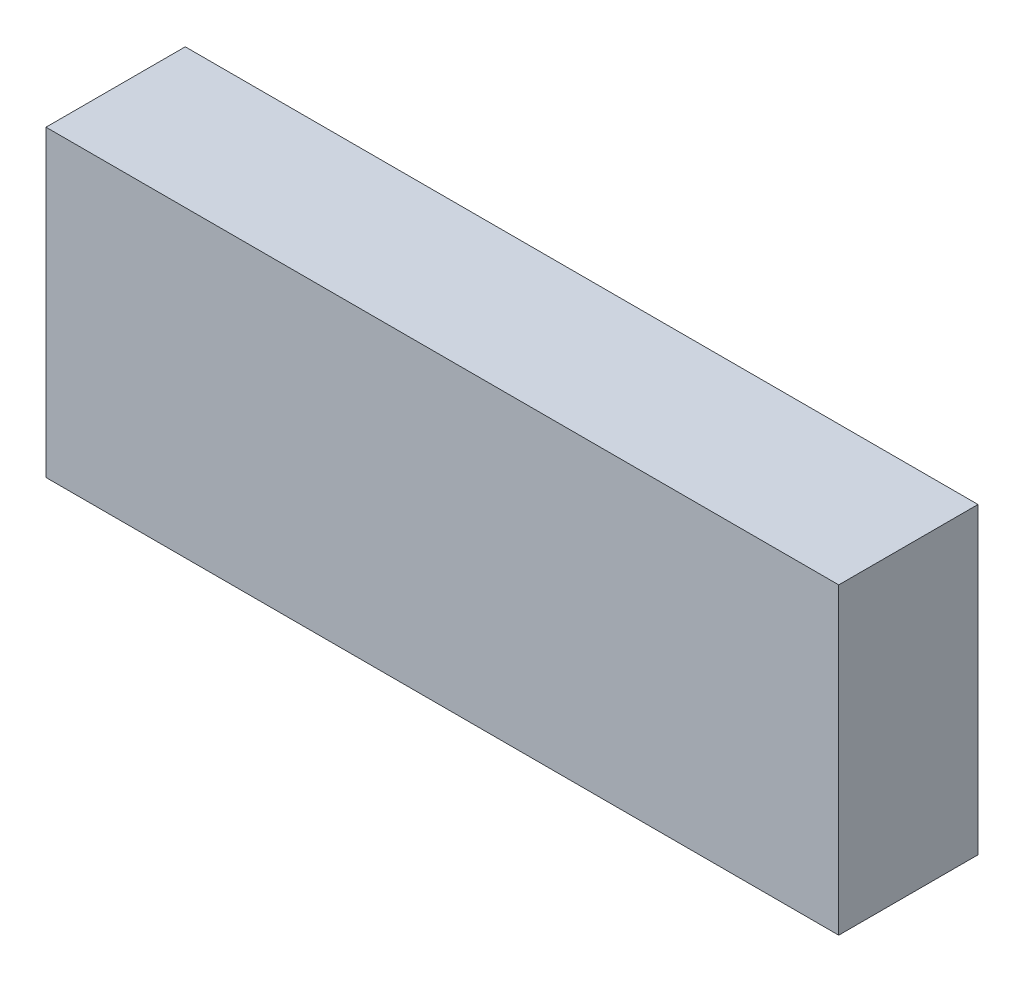
SolidWorks part; units mm, degrees
ref_plane "Front Plane" through (0, 0, 0) normal (0, 0, 1) x (1, 0, 0)
ref_plane "Top Plane" through (0, 0, 0) normal (0, 1, 0) x (1, 0, 0)
ref_plane "Right Plane" through (0, 0, 0) normal (1, 0, 0) x (0, 0, -1)
sketch "Sketch2" plane through (0, 0, 0) normal (0, 1, 0) x (1, 0, 0)
  line L0 (-50.2626, 2.7131) -> (-50.2626, -15.1869)
  line L5 (-50.2626, -15.1869) -> (51.6374, -15.1869)
  line L6 (51.6374, 2.7131) -> (51.6374, -15.1869)
  line L7 (-50.2626, 2.7131) -> (51.6374, 2.7131)
  line L8 (-51.2126, 3.6631) -> (-51.2126, -16.1369)
  line L9 (-51.2126, -16.1369) -> (52.5874, -16.1369)
  line L10 (52.5874, 3.6631) -> (52.5874, -16.1369)
  line L11 (-51.2126, 3.6631) -> (52.5874, 3.6631)
  dimension "D4" = 0.95
extrude "Boss-Extrude1" add sketch "Sketch2" along normal blind 39 contours L0 L5 L6 L7
